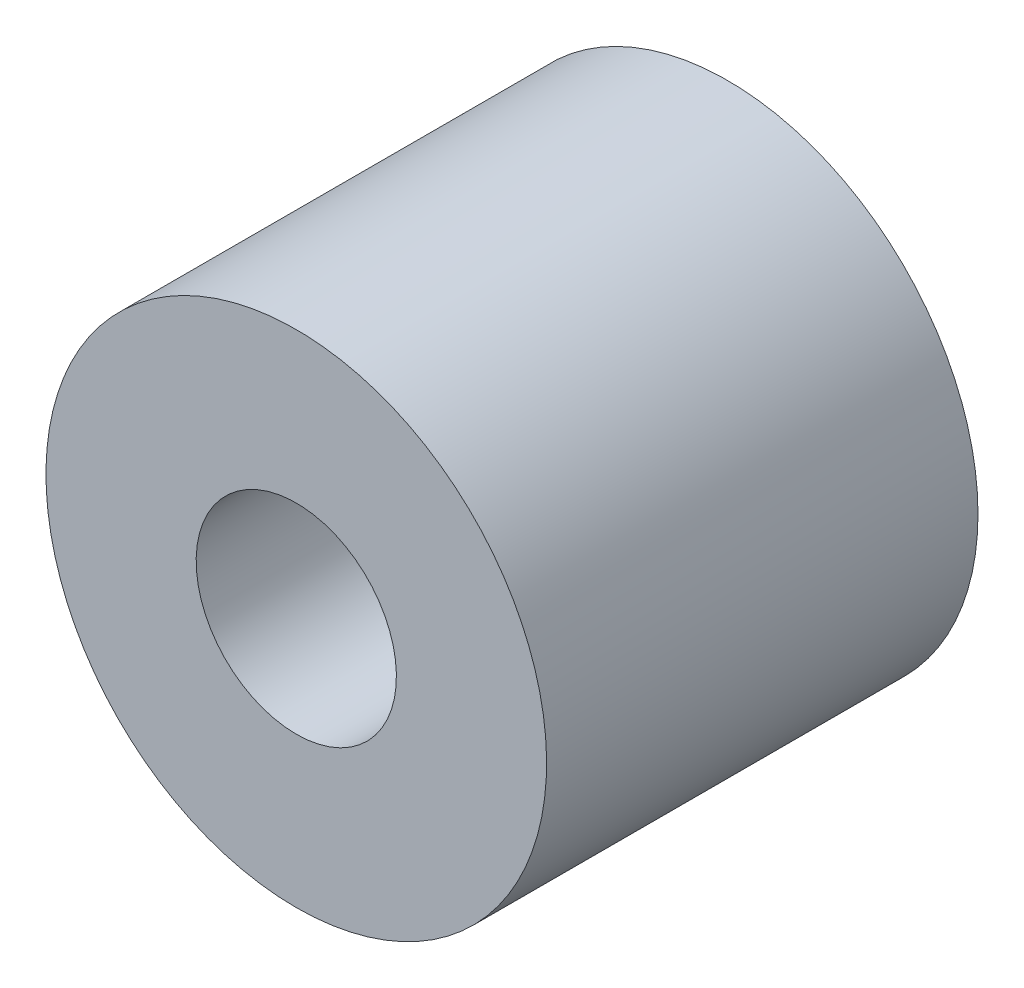
SolidWorks part; units mm, degrees
ref_plane "Front Plane" through (0, 0, 0) normal (0, 0, 1) x (1, 0, 0)
ref_plane "Top Plane" through (0, 0, 0) normal (0, 1, 0) x (1, 0, 0)
ref_plane "Right Plane" through (0, 0, 0) normal (1, 0, 0) x (0, 0, -1)
sketch "Sketch1" plane through (0, 0, 0) normal (0, 0, 1) x (1, 0, 0)
  circle A0 centre (-70, 14.1421) radius 3 construction
  circle A1 centre (-70, 14.1421) radius 3
  circle A2 centre (-70, 14.1421) radius 7.5
  arc A3 (-70, 21.6421) -> (-72.9354, 7.2405) centre (-70, 14.1421) ccw construction
extrude "Boss-Extrude1" add sketch "Sketch1" along normal up to surface (12.925 mm away)
